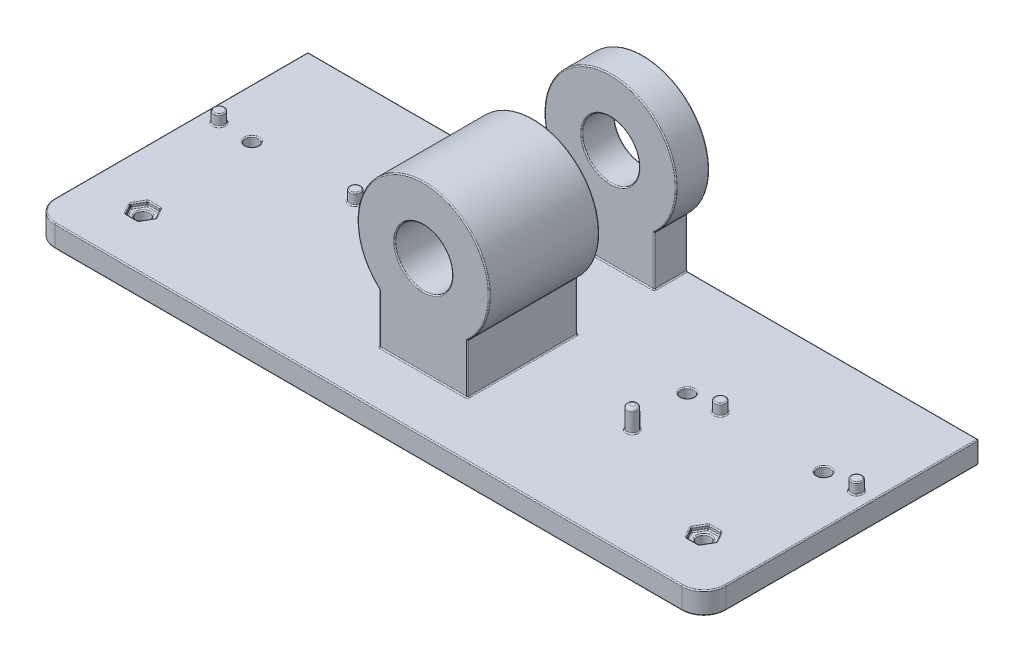
SolidWorks part; units mm, degrees
ref_plane "Front Plane" through (0, 0, 0) normal (0, 0, 1) x (1, 0, 0)
ref_plane "Top Plane" through (0, 0, 0) normal (0, 1, 0) x (1, 0, 0)
ref_plane "Right Plane" through (0, 0, 0) normal (1, 0, 0) x (0, 0, -1)
sketch "Sketch1" plane through (0, 0, 0) normal (0, 1, 0) x (1, 0, 0)
  line L0 (152.5, 125) -> (152.5, 0) construction
  line L1 (0, 0) -> (305, 0)
  line L2 (0, 0) -> (0, 125)
  line L3 (0, 125) -> (305, 125)
  line L4 (305, 0) -> (305, 125)
  line L5 (25, 100) -> (280, 100) construction
  line L6 (280, 25) -> (280, 100) construction
  line L7 (25, 25) -> (280, 25) construction
  line L8 (25, 25) -> (25, 100) construction
  line L9 (152.5, 62.5) -> (25, 62.5) construction
  line L10 (30.7735, 100) -> (27.8868, 105) construction
  line L11 (27.8868, 105) -> (22.1132, 105) construction
  line L12 (22.1132, 105) -> (19.2265, 100) construction
  line L13 (19.2265, 100) -> (22.1132, 95) construction
  line L14 (22.1132, 95) -> (27.8868, 95) construction
  line L15 (27.8868, 95) -> (30.7735, 100) construction
  line L16 (27.8868, 30) -> (30.7735, 25) construction
  line L17 (22.1132, 30) -> (27.8868, 30) construction
  line L18 (19.2265, 25) -> (22.1132, 30) construction
  line L19 (22.1132, 20) -> (19.2265, 25) construction
  line L20 (27.8868, 20) -> (22.1132, 20) construction
  line L21 (30.7735, 25) -> (27.8868, 20) construction
  line L22 (282.8868, 30) -> (277.1132, 30) construction
  line L23 (285.7735, 25) -> (282.8868, 30) construction
  line L24 (282.8868, 20) -> (285.7735, 25) construction
  line L25 (277.1132, 20) -> (282.8868, 20) construction
  line L26 (274.2265, 25) -> (277.1132, 20) construction
  line L27 (277.1132, 30) -> (274.2265, 25) construction
  line L28 (277.1132, 95) -> (274.2265, 100) construction
  line L29 (282.8868, 95) -> (277.1132, 95) construction
  line L30 (285.7735, 100) -> (282.8868, 95) construction
  line L31 (282.8868, 105) -> (285.7735, 100) construction
  line L32 (277.1132, 105) -> (282.8868, 105) construction
  line L33 (274.2265, 100) -> (277.1132, 105) construction
  line L34 (172.5, 75) -> (172.5, 125) construction
  line L35 (132.5, 0) -> (172.5, 0) construction
  line L36 (132.5, 0) -> (132.5, 125) construction
  line L37 (132.5, 125) -> (172.5, 125) construction
  line L38 (172.5, 0) -> (172.5, 125) construction
  line L39 (132.5, 75) -> (172.5, 75) construction
  line L40 (132.5, 75) -> (132.5, 25) construction
  line L41 (132.5, 25) -> (172.5, 25) construction
  line L42 (172.5, 75) -> (172.5, 25) construction
  line L51 (0, 84.5) -> (15, 69.5) construction
  line L52 (132.5, 75) -> (117.5, 60) construction
  line L53 (117.5, 60) -> (117.5, 85) construction
  line L54 (0, 125) -> (108, 125) construction
  line L55 (0, 125) -> (0, 84.5) construction
  line L56 (0, 84.5) -> (108, 84.5) construction
  line L57 (108, 125) -> (108, 84.5) construction
  line L58 (15, 69.5) -> (15, 84.5) construction
  line L59 (30, 84.5) -> (0, 84.5) construction
  line L60 (30, 84.5) -> (30, 69.5) construction
  line L61 (30, 69.5) -> (0, 69.5) construction
  line L62 (0, 84.5) -> (0, 69.5) construction
  line L63 (92, 84.5) -> (92, 69.5) construction
  line L64 (62, 0) -> (62, 125) construction
  circle A1 centre (25, 100) radius 5 construction
  circle A3 centre (280, 25) radius 3
  circle A4 centre (25, 25) radius 3
  circle A8 centre (117.5, 60) radius 3
  circle A9 centre (117.5, 85) radius 3
  circle A10 centre (7.5, 77) radius 3 construction
  circle A11 centre (22.5, 77) radius 3
  circle A12 centre (69.5, 77) radius 3 construction
  circle A13 centre (84.5, 77) radius 3
  circle A14 centre (220.5, 77) radius 3
  circle A15 centre (235.5, 77) radius 3 construction
  circle A16 centre (282.5, 77) radius 3
  circle A17 centre (297.5, 77) radius 3 construction
  dimension "D3" = 6
  dimension "D1" = 305
  dimension "D2" = 125
  dimension "D5" = 10
  dimension "D6" = 40
  dimension "D8" = 50
  dimension "D12" = 15
  dimension "D7" = 40.5
  dimension "D9" = 108
  dimension "D10" = 15
  dimension "D11" = 30
  dimension "D15" = 62
  dimension "D16" = 15
  dimension "D17" = 25
  dimension "D4" = 25
  dimension "D13" = 2
  dimension "D14" = 2
extrude "Boss-Extrude1" add sketch "Sketch1" along normal blind 10
sketch "Sketch6" plane through (0, 10, 0) normal (0, 1, 0) x (1, 0, 0)
  line L0 (152.5, 125) -> (152.5, 0) construction
  line L7 (305, 125) -> (0, 125) construction
  line L8 (0, 0) -> (305, 0) construction
  line L9 (152.5, 62.5) -> (0, 62.5) construction
  line L10 (0, 125) -> (0, 0) construction
  line L29 (27.8868, 30) -> (30.7735, 25)
  line L30 (274.2265, 25) -> (277.1132, 20)
  line L31 (277.1132, 20) -> (282.8868, 20)
  line L32 (282.8868, 20) -> (285.7735, 25)
  line L33 (285.7735, 25) -> (282.8868, 30)
  line L34 (282.8868, 30) -> (277.1132, 30)
  line L35 (277.1132, 30) -> (274.2265, 25)
  line L36 (22.1132, 30) -> (27.8868, 30)
  line L37 (19.2265, 25) -> (22.1132, 30)
  line L38 (22.1132, 20) -> (19.2265, 25)
  line L39 (27.8868, 20) -> (22.1132, 20)
  line L40 (30.7735, 25) -> (27.8868, 20)
  circle A0 centre (280, 25) radius 5 construction
  dimension "D1" = 10
extrude "Cut-Extrude1" cut sketch "Sketch6" against normal blind 2
sketch "Sketch7" plane through (0, 10, 0) normal (0, 1, 0) x (1, 0, 0)
  line L0 (0, 0) -> (305, 0) construction
  line L1 (132.5, 25) -> (172.5, 25)
  line L2 (132.5, 25) -> (132.5, 75)
  line L3 (132.5, 75) -> (172.5, 75)
  line L4 (172.5, 25) -> (172.5, 75)
  line L5 (152.5, 0) -> (152.5, 125) construction
  line L6 (305, 125) -> (0, 125) construction
  line L7 (172.5, 75) -> (172.5, 125) construction
  line L18 (132.5, 110) -> (172.5, 110)
  line L19 (132.5, 110) -> (132.5, 125)
  line L20 (132.5, 125) -> (172.5, 125)
  line L21 (172.5, 110) -> (172.5, 125)
  point P11 (152.5, 75)
  point P20 (152.5, 110)
  dimension "D1" = 40
  dimension "D4" = 15
extrude "Boss-Extrude2" add sketch "Sketch7" along normal blind 22.6393
sketch "Sketch11" plane through (0, 0, -25) normal (0, 0, 1) x (1, 0, 0)
  circle A0 centre (152.5, 55) radius 30
  circle A1 centre (152.5, 55) radius 13
  dimension "D1" = 60
  dimension "D2" = 26
extrude "Boss-Extrude3" add sketch "Sketch11" against normal up to surface (100 mm away) up to face at (152.5, 13.1598, -125)
ref_plane "Plane1" through (0, 0, -62.5) normal (0, 0, 1) x (1, 0, 0)
sketch "Sketch12" plane through (305, 0, 0) normal (1, 0, 0) x (0, 0, -1)
  line L0 (125, 85) -> (25, 85) construction
  line L1 (75, 10) -> (110, 10)
  line L2 (75, 10) -> (75, 85)
  line L3 (75, 85) -> (110, 85)
  line L4 (110, 10) -> (110, 85)
  line L6 (110, 32.6393) -> (110, 10) construction
extrude "Cut-Extrude2" cut sketch "Sketch12" against normal through all
sketch "Sketch13" plane through (0, 10, 0) normal (0, 1, 0) x (1, 0, 0)
  line L0 (222.5, 50) -> (172.5, 50) construction
  line L1 (172.5, 25) -> (172.5, 75) construction
  circle A1 centre (222.5, 50) radius 2.4
  dimension "D1" = 4.8
  dimension "D2" = 50
extrude "Boss-Extrude4" add sketch "Sketch13" along normal blind 10
fillet "Fillet1" radius 1.3 1 edges at (222.5, 20, -47.6)
sketch "Sketch15" plane through (0, 10, 0) normal (0, 1, 0) x (1, 0, 0)
  line L0 (69.5, 77) -> (7.5, 77) construction
  line L1 (38.5, 77) -> (38.5, 84.5) construction
  line L2 (0, 84.5) -> (108, 84.5) construction
  line L3 (152.5, 125) -> (152.5, 0) construction
  circle A1 centre (69.5, 77) radius 2.5
  circle A2 centre (7.5, 77) radius 2.5
  circle A3 centre (7.5, 77) radius 2.5
  circle A4 centre (235.5, 77) radius 2.5
  circle A5 centre (297.5, 77) radius 2.5
  dimension "D1" = 0.5
extrude "Boss-Extrude5" add sketch "Sketch15" along normal blind 5
chamfer "Chamfer1" distance 3.3 angle 45 6 edges at (282.5, 0, -74) (220.5, 0, -74) (84.5, 0, -80) (22.5, 0, -80) (117.5, 0, -57) (117.5, 0, -82)
fillet "Fillet2" radius 0.5 93 edges at (25, 0, -28) (19.2265, 9, -25) (22.1132, 9, -20) (27.8868, 9, -30) (22.1132, 9, -30) (27.8868, 9, -20) (30.7735, 9, -25) (29.3301, 8, -27.5) (29.3301, 8, -22.5) (25, 8, -20) (20.6699, 8, -22.5) (20.6699, 8, -27.5) (25, 8, -30) (25, 8, -28) (280, 0, -22) (277.1132, 9, -30) (274.2265, 9, -25) (285.7735, 9, -25) (282.8868, 9, -30) (277.1132, 9, -20) (282.8868, 9, -20) (280, 8, -30) (284.3301, 8, -27.5) (284.3301, 8, -22.5) (280, 8, -20) (275.6699, 8, -22.5) (275.6699, 8, -27.5) (280, 8, -22) (235.5, 15, -74.5) (297.5, 15, -79.5) (69.5, 15, -79.5) (7.5, 15, -74.5) (117.5, 10, -57) (280, 10, -20) (284.3301, 10, -22.5) (284.3301, 10, -27.5) (280, 10, -30) (275.6699, 10, -27.5) (275.6699, 10, -22.5) (20.6699, 10, -22.5) (25, 10, -20) (29.3301, 10, -22.5) (29.3301, 10, -27.5) (25, 10, -30) (20.6699, 10, -27.5) (117.5, 10, -82) (305, 10, -62.5) (152.5, 10, 0) (0, 10, -62.5) (22.5, 10, -80) (84.5, 10, -80) (220.5, 10, -74) (282.5, 10, -74) (222.5, 10, -52.4) (7.5, 10, -79.5) (69.5, 10, -79.5) (235.5, 10, -79.5) (297.5, 10, -79.5) (165.5, 55, -25) (152.5, 10, -25) (152.5, 85, -25) (132.5, 32.6393, -50) (132.5, 21.3197, -25) (132.5, 10, -50) (165.5, 55, -75) (152.5, 10, -75) (152.5, 85, -75) (132.5, 21.3197, -75) (172.5, 21.3197, -25) (172.5, 32.6393, -50) (172.5, 21.3197, -75) (172.5, 10, -50) (172.5, 32.6393, -117.5) (172.5, 10, -117.5) (132.5, 32.6393, -117.5) (132.5, 10, -117.5) (165.5, 55, -125) (66.25, 10, -125) (0, 5, -125) (152.5, 0, -125) (305, 5, -125) (238.75, 10, -125) (172.5, 21.3197, -125) (152.5, 85, -125) (132.5, 21.3197, -125) (139.5, 55, -110) (152.5, 10, -110) (132.5, 21.3197, -110) (152.5, 85, -110) (172.5, 21.3197, -110) (305, 0, -62.5) (152.5, 0, 0) (0, 0, -62.5)
fillet "Fillet3" radius 10 6 edges at (0.1464, 0.1464, -0.1464) (0.1464, 9.8536, -0.1464) (304.8536, 0.1464, -0.1464) (304.8536, 9.8536, -0.1464) (305, 5, 0) (0, 5, 0)
equation "\"joint_width\"=4"
equation "\"D2@Sketch7\"=5"
equation "\"short_base_length\"=12.5"
equation "\"D2@Sketch1\"=\"short_base_length\""
equation "\"outer_diam_main_joint\"=6"
equation "\"D1@Sketch11\"=\"outer_diam_main_joint\""
equation "\"D1@Sketch7\"=\"outer_diam_main_joint\"-2"
equation "\"D1@Boss-Extrude2\"=(\"outer_diam_main_joint\"/2)+1.5cm-sqr((\"outer_diam_main_joint\"/2)^2-((\"outer_diam_main_joint\"-2)/2)^2)"
equation "\"D6@Sketch1\"=\"outer_diam_main_joint\"-2"
equation "\"pulleyside\"=1.5"
